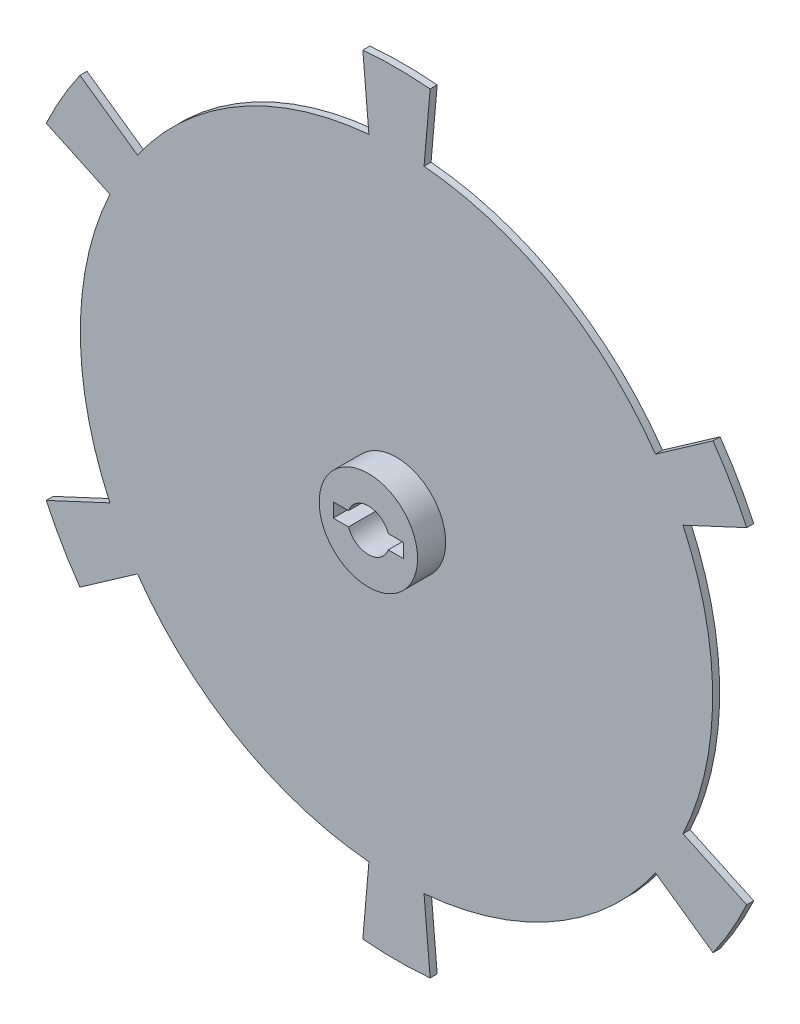
SolidWorks part; units mm, degrees
ref_plane "Front" through (0, 0, 0) normal (0, 0, 1) x (1, 0, 0)
ref_plane "Top" through (0, 0, 0) normal (0, 1, 0) x (1, 0, 0)
ref_plane "Right" through (0, 0, 0) normal (1, 0, 0) x (0, 0, -1)
sketch "Sketch1" plane through (0, 0, 0) normal (0, 0, 1) x (1, 0, 0)
  line L0 (28.2843, -10) -> (50, -10)
  line L1 (-50, 10) -> (-28.2843, 10)
  line L2 (-50, 10) -> (-50, -10)
  line L3 (-50, -10) -> (-28.2843, -10)
  line L4 (50, 10) -> (50, -10)
  line L5 (28.2843, 10) -> (50, 10)
  circle A0 centre (0, 0) radius 450
  arc A1 (28.2843, 10) -> (-28.2843, 10) centre (0, 0) ccw
  arc A2 (-28.2843, -10) -> (28.2843, -10) centre (0, 0) ccw
extrude "Boss-Extrude1" add sketch "Sketch1" along normal blind 10
sketch "Sketch2" plane through (0, 0, 10) normal (0, 0, 1) x (1, 0, 0)
  line L0 (-50, 10) -> (-50, -10)
  line L1 (-50, -10) -> (-28.2843, -10)
  line L2 (-50, 10) -> (-28.2843, 10)
  line L3 (28.2843, 10) -> (50, 10)
  line L4 (50, 10) -> (50, -10)
  line L5 (50, -10) -> (28.2843, -10)
  circle A0 centre (0, 0) radius 70
  arc A1 (-28.2843, -10) -> (28.2843, -10) centre (0, 0) ccw
  arc A2 (28.2843, 10) -> (-28.2843, 10) centre (0, 0) ccw
extrude "Boss-Extrude2" add sketch "Sketch2" along normal blind 40
sketch "Sketch3" plane through (0, 0, 10) normal (0, 0, 1) x (1, 0, 0)
  line L0 (0, 0) -> (-47.9357, 547.9071)
  line L1 (47.9357, 547.9071) -> (0, 0)
  line L2 (0, 0) -> (450.5336, 315.467)
  line L3 (498.4693, 232.44) -> (0, 0)
  line L4 (0, 0) -> (498.4693, -232.44)
  line L5 (450.5336, -315.467) -> (0, 0)
  line L6 (0, 0) -> (47.9357, -547.9071)
  line L7 (-47.9357, -547.9071) -> (0, 0)
  line L8 (0, 0) -> (-450.5336, -315.467)
  line L9 (-498.4693, -232.44) -> (0, 0)
  line L10 (0, 0) -> (-498.4693, 232.44)
  line L11 (-450.5336, 315.467) -> (0, 0)
  line L12 (0, 0) -> (0, 450)
  arc A0 (-47.9357, 547.9071) -> (47.9357, 547.9071) centre (0, 0) cw
  arc A1 (450.5336, 315.467) -> (498.4693, 232.44) centre (0, 0) cw
  arc A2 (498.4693, -232.44) -> (450.5336, -315.467) centre (0, 0) cw
  arc A3 (47.9357, -547.9071) -> (-47.9357, -547.9071) centre (0, 0) cw
  arc A4 (-450.5336, -315.467) -> (-498.4693, -232.44) centre (0, 0) cw
  arc A5 (-498.4693, 232.44) -> (-450.5336, 315.467) centre (0, 0) cw
  circle A6 centre (0, 0) radius 400
  circle M1 centre (0, 0) radius 450
extrude "Boss-Extrude3" add sketch "Sketch3" along direction (0, 0, 1) on the side against the normal up to surface (10 mm away) contours A5 L10 L11 M1 | A0 L0 L1 M1 | A1 L2 L3 M1 | A2 L4 L5 M1 | A3 L6 L7 M1 | A4 L8 L9 M1 region at (0, 501.0302, 10) region at (433.9049, 250.5151, 10) region at (433.9049, -250.5151, 10) region at (0, -501.0302, 10) region at (-433.9049, -250.5151, 10) region at (-433.9049, 250.5151, 10) up to face at (450, 0, 0)
